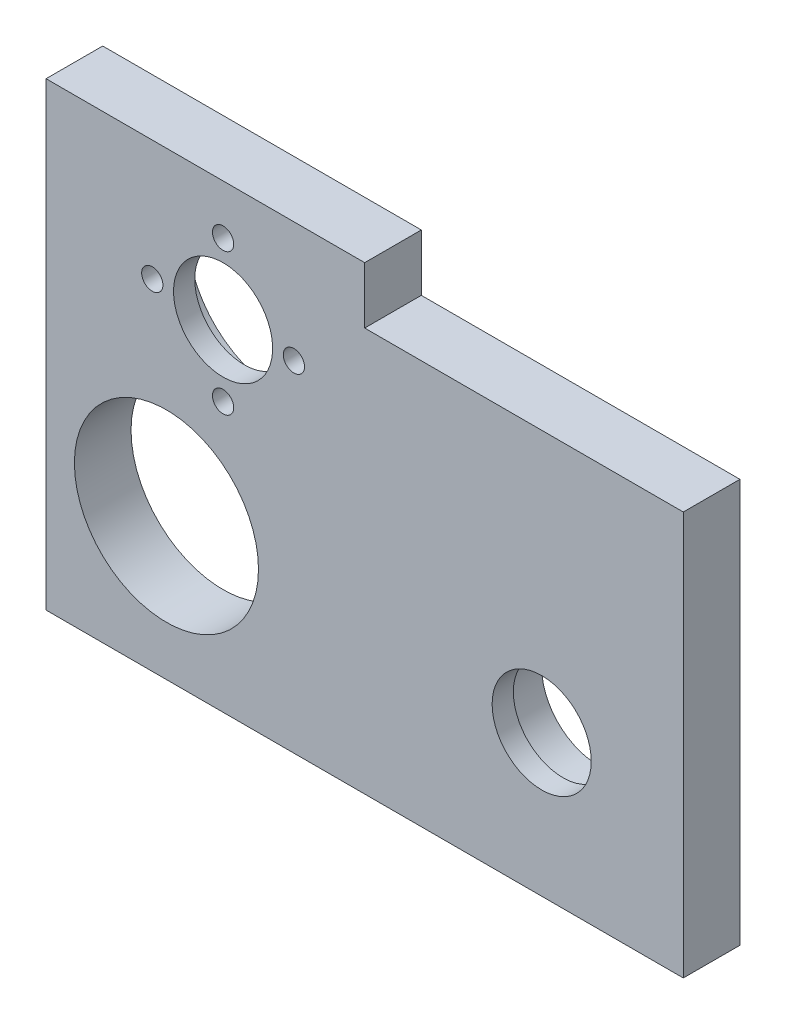
SolidWorks part; units mm, degrees
ref_plane "Front" through (0, 0, 0) normal (0, 0, 1) x (1, 0, 0)
ref_plane "Top" through (0, 0, 0) normal (0, 1, 0) x (1, 0, 0)
ref_plane "Right" through (0, 0, 0) normal (1, 0, 0) x (0, 0, -1)
sketch "Esquisse1" plane through (0, 0, 0) normal (0, 0, 1) x (1, 0, 0)
  line L1 (0, 0) -> (90, 0)
  line L2 (0, 0) -> (0, 65)
  line L3 (0, 65) -> (90, 65)
  line L4 (90, 0) -> (90, 65)
  circle A0 centre (70, 20) radius 7
  circle A1 centre (17, 20) radius 13
  circle A2 centre (25, 48) radius 13
  dimension "D3" = 14
  dimension "D4" = 20
  dimension "D6" = 53
  dimension "D8" = 26
  dimension "D9" = 26
  dimension "D1" = 90
  dimension "D2" = 65
  dimension "D5" = 70
  dimension "D7" = 20
  dimension "D10" = 53
  dimension "D11" = 48
extrude "Boss.-Extru.1" add sketch "Esquisse1" along normal blind 8
sketch "Esquisse2" plane through (0, 0, 0) normal (0, 0, -1) x (-1, 0, 0)
  circle A0 centre (-25, 48) radius 13
  circle A1 centre (-17, 20) radius 13 construction
extrude "Boss.-Extru.2" add sketch "Esquisse2" along normal blind 3 from surface starting at face at (45, 32.5, 8)
sketch "Esquisse3" plane through (0, 0, 5) normal (0, 0, -1) x (-1, 0, 0)
  line L0 (-15, 48) -> (-25, 48) construction
  circle A0 centre (-25, 48) radius 7
  circle A1 centre (-15, 48) radius 1.5
  circle A2 centre (-25, 38) radius 1.5
  circle A3 centre (-35, 48) radius 1.5
  circle A4 centre (-25, 58) radius 1.5
  point P13 (-25, 48)
  dimension "D1" = 14
  dimension "D2" = 3
  dimension "D3" = 10
  dimension "D4" = 4
extrude "Enlèv. mat.-Extru.1" cut sketch "Esquisse3" against normal through all
sketch "Esquisse4" plane through (0, 0, 8) normal (0, 0, 1) x (1, 0, 0)
  circle A0 centre (70, 20) radius 8
  dimension "D1" = 16
extrude "Enlèv. mat.-Extru.2" cut sketch "Esquisse4" along normal blind 5 from surface starting at face at (30, 20, 0)
sketch "Esquisse5" plane through (0, 0, 0) normal (0, 0, -1) x (-1, 0, 0)
  line L1 (-90, 65) -> (-45, 65)
  line L2 (-90, 65) -> (-90, 57)
  line L3 (-90, 57) -> (-45, 57)
  line L4 (-45, 65) -> (-45, 57)
  dimension "D1" = 8
  dimension "D2" = 45
extrude "Enlèv. mat.-Extru.3" cut sketch "Esquisse5" against normal through all
